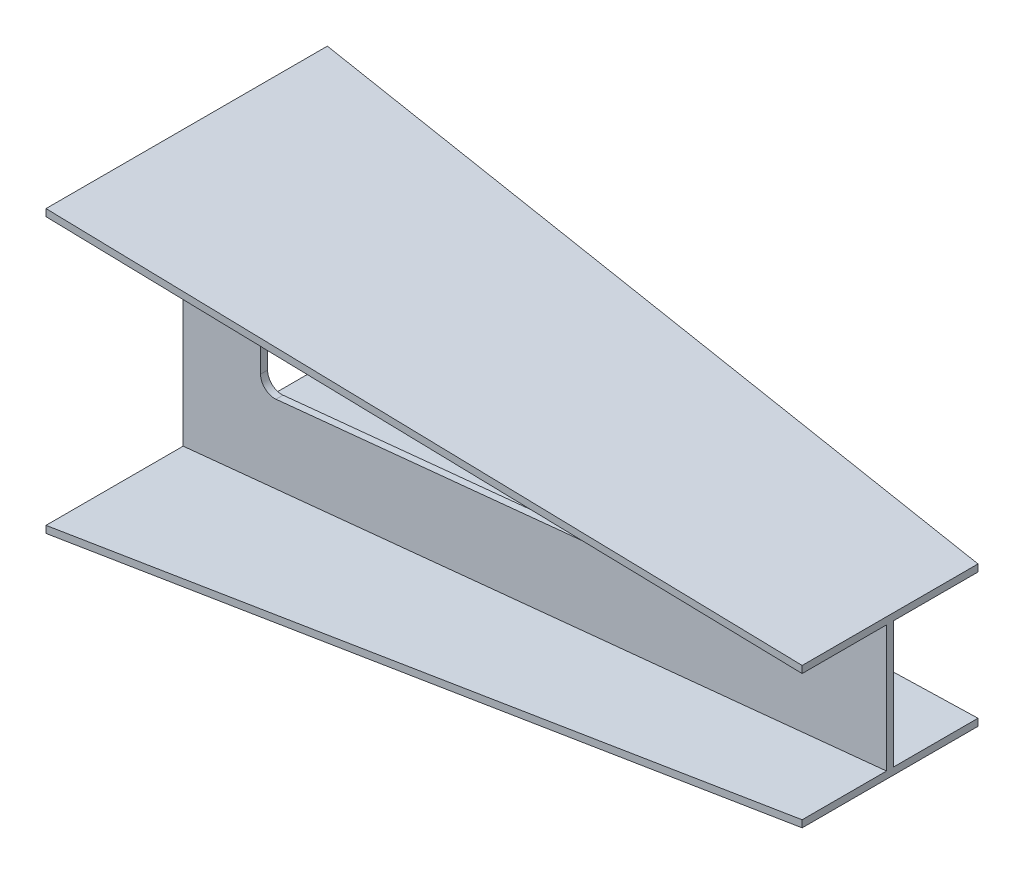
SolidWorks part; units mm, degrees
ref_plane "Front Plane" through (0, 0, 0) normal (0, 0, 1) x (1, 0, 0)
ref_plane "Top Plane" through (0, 0, 0) normal (0, 1, 0) x (1, 0, 0)
ref_plane "Right Plane" through (0, 0, 0) normal (1, 0, 0) x (0, 0, -1)
sketch "Sketch1" plane through (0, 0, 0) normal (1, 0, 0) x (0, 0, -1)
  line L1 (-205, 200) -> (195, 200)
  line L2 (-205, 200) -> (-205, 190)
  line L4 (195, 200) -> (195, 190)
  line L6 (-205, -190) -> (-205, -200)
  line L7 (-205, -200) -> (195, -200)
  line L8 (195, -190) -> (195, -200)
  line L15 (-205, -190) -> (-10, -190)
  line L16 (-5, 190) -> (-5, -790) construction
  line L18 (-205, 190) -> (-10, 190)
  line L19 (0, 0) -> (192.2403, 0) construction
  line L21 (-10, 190) -> (-10, -190)
  line L23 (0, 190) -> (0, -190)
  line L27 (0, 190) -> (195, 190)
  line L28 (0, -190) -> (195, -190)
  dimension "D2" = 10
  dimension "D1" = 400
  dimension "D3" = 400
  dimension "D4" = 10
ref_plane "Plane2" through (1000, 0, 0) normal (1, 0, 0) x (0, 0, -1)
sketch "Sketch4" plane through (1000, 0, -1000) normal (-1, 0, 0) x (0, 0, 1)
  line L1 (880, 100) -> (1130, 100)
  line L2 (880, 100) -> (880, 90)
  line L4 (1130, 100) -> (1130, 90)
  line L6 (880, -90) -> (880, -100)
  line L7 (880, -100) -> (1130, -100)
  line L8 (1130, -90) -> (1130, -100)
  line L15 (880, -90) -> (1000, -90)
  line L16 (1005, 390) -> (1005, -390) construction
  line L18 (880, 90) -> (1000, 90)
  line L19 (1010, -90) -> (1130, -90)
  line L21 (1000, 90) -> (1000, -90)
  line L23 (1010, 90) -> (1010, -90)
  line L24 (1010, 90) -> (1130, 90)
  line L26 (1010, 190) -> (1010, -190) construction
  line L27 (1000, 0) -> (820.2065, 0) construction
  dimension "D1" = 250
  dimension "D2" = 10
  dimension "D3" = 200
  dimension "D4" = 10
loft "Loft4" add profiles "Sketch1", "Sketch4" connector at (0, 190, 10) connector at (1000, 90, 10)
sketch "Sketch5" plane through (0, 0, 10) normal (0, 0, 1) x (1, 0, 0)
  line L8 (110, -68.4514) -> (794.5137, 0)
  line L9 (794.5137, 0) -> (110, 68.4514)
  line L10 (110, 68.4514) -> (110, -68.4514)
  line L11 (131.9901, -66.2524) -> (595.5062, -19.9007)
  line L12 (595.5062, 19.9007) -> (131.9901, 66.2524)
  line L13 (110, 46.3516) -> (110, -46.3516)
  arc A0 (595.5062, -19.9007) -> (595.5062, 19.9007) centre (593.5162, 0) ccw
  arc A1 (131.9901, -66.2524) -> (110, -46.3516) centre (130, -46.3516) cw
  arc A2 (131.9901, 66.2524) -> (110, 46.3516) centre (130, 46.3516) ccw
  dimension "D2" = 20
  dimension "D1" = 110
extrude "Cut-Extrude1" cut sketch "Sketch5" against normal through all
equation "\"ANS_h1\"=200"
equation "\"D3@Sketch4\"=\"ANS_h1\""
equation "\"ANS_w1\"=250"
equation "\"D1@Sketch4\"=\"ANS_w1\""
equation "\"ANS_h2\"=400"
equation "\"D3@Sketch1\"=\"ANS_h2\""
equation "\"ANS_w2\"=400"
equation "\"D1@Sketch1\"=\"ANS_w2\""
